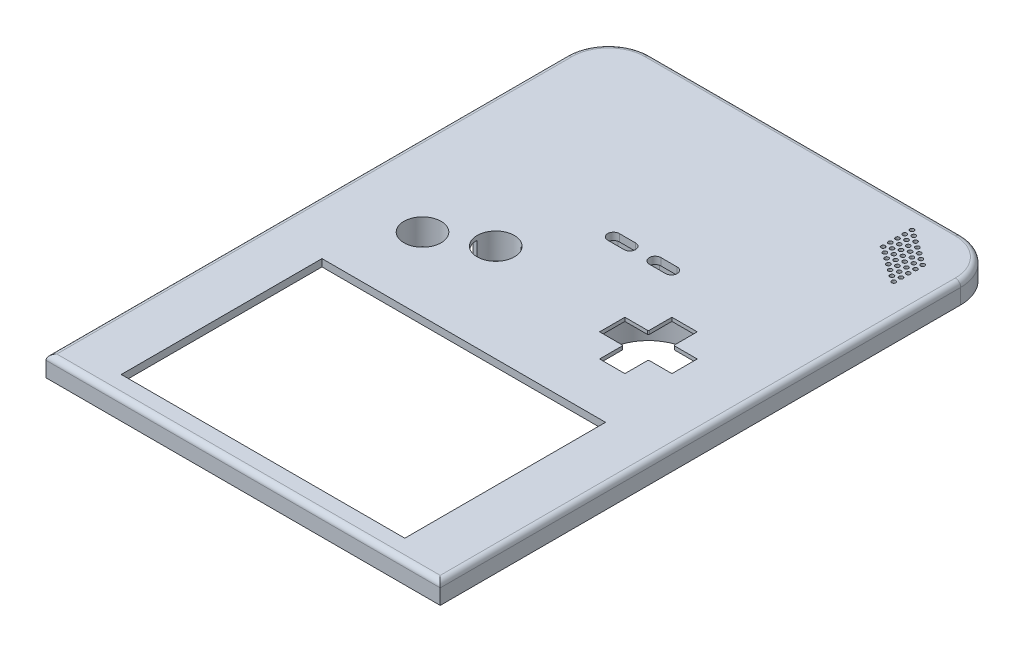
SolidWorks part; units mm, degrees
ref_plane "Front Plane" through (0, 0, 0) normal (0, 0, 1) x (1, 0, 0)
ref_plane "Top Plane" through (0, 0, 0) normal (0, 1, 0) x (1, 0, 0)
ref_plane "Right Plane" through (0, 0, 0) normal (1, 0, 0) x (0, 0, -1)
sketch "Sketch1" plane through (0, 0, 0) normal (0, 1, 0) x (1, 0, 0)
  line L1 (-54.5, 77.75) -> (54.5, 77.75)
  line L2 (-54.5, 77.75) -> (-54.5, -77.75)
  line L3 (-54.5, -77.75) -> (54.5, -77.75)
  line L4 (54.5, 77.75) -> (54.5, -77.75)
  line L5 (-54.5, 77.75) -> (54.5, -77.75) construction
  line L6 (-54.5, -77.75) -> (54.5, 77.75) construction
  point P0 (0, 0)
  dimension "D1" = 109
  dimension "D2" = 155.5
extrude "Boss-Extrude1" add sketch "Sketch1" along normal blind 5.7
sketch "Sketch2" plane through (0, 0, 0) normal (0, -1, 0) x (-1, 0, 0)
  line L1 (-52.45, 75.7) -> (52.45, 75.7)
  line L2 (-52.45, 75.7) -> (-52.45, -75.7)
  line L3 (-52.45, -75.7) -> (52.45, -75.7)
  line L4 (52.45, 75.7) -> (52.45, -75.7)
  line L5 (-52.45, 75.7) -> (52.45, -75.7) construction
  line L6 (-52.45, -75.7) -> (52.45, 75.7) construction
  point P0 (0, 0)
  dimension "D1" = 151.4
  dimension "D2" = 104.9
extrude "Cut-Extrude1" cut sketch "Sketch2" against normal blind 3.7
sketch "Sketch3" plane through (0, 5.7, 0) normal (0, 1, 0) x (1, 0, 0)
  line L1 (42.9, 66.15) -> (54.5, 66.15)
  line L2 (54.5, -77.75) -> (54.5, 77.75) construction
  line L4 (31.3, 66.15) -> (31.3, 77.75)
  line L7 (54.5, 66.15) -> (54.5, 77.75)
  line L8 (54.5, 77.75) -> (42.9, 77.75)
  line L9 (42.9, 77.75) -> (42.9, 66.15)
  line L10 (54.5, -77.75) -> (54.5, 77.75) construction
  line L11 (54.5, 77.75) -> (-54.5, 77.75) construction
  line L12 (0, -77.75) -> (0, 77.75) construction
  line L17 (-54.5, -77.75) -> (54.5, -77.75) construction
  line L19 (54.5, 77.75) -> (-54.5, 77.75) construction
  line L21 (-54.5, 77.75) -> (-42.9, 77.75)
  line L22 (-54.5, 66.15) -> (-54.5, 77.75)
  line L25 (-42.9, 77.75) -> (-42.9, 66.15)
  line L26 (-42.9, 66.15) -> (-54.5, 66.15)
  circle A1 centre (42.9, 66.15) radius 11.6
  circle A2 centre (42.9, 66.15) radius 9.55
  circle A5 centre (-42.9, 66.15) radius 9.55
  circle A6 centre (-42.9, 66.15) radius 11.6
  line M2 (54.5, -77.75) -> (54.5, 77.75)
  line M3 (54.5, 77.75) -> (-54.5, 77.75)
  line M4 (-54.5, 77.75) -> (-54.5, -77.75)
  dimension "D1" = 23.2
  dimension "D2" = 19.1
  dimension "D3" = 23.2
extrude "Cut-Extrude3" cut sketch "Sketch3" against normal through all contours A1 M2 M3 region at (51.9089, 5.7, -75.1589)
sketch "Sketch15" plane through (0, 3.7, 0) normal (0, -1, 0) x (1, 0, 0)
  line L5 (42.9, -77.75) -> (-54.5, -77.75) construction
  line L8 (54.5, 77.75) -> (54.5, -66.15) construction
  circle A0 centre (41.14, -64.39) radius 12.3
  circle A1 centre (41.14, -64.39) radius 11.3
  dimension "D1" = 24.6
  dimension "D2" = 22.6
  dimension "D3" = 13.36
  dimension "D4" = 13.36
extrude "Boss-Extrude27" add sketch "Sketch15" along normal blind 3.15
sketch "Sketch4" plane through (0, 5.7, 0) normal (0, 1, 0) x (1, 0, 0)
  line L0 (54.5, -44.5) -> (-54.5, -44.5) construction
  line L1 (-54.5, -77.75) -> (54.5, -77.75) construction
  line L4 (-54.5, 77.75) -> (-54.5, -77.75) construction
  line L5 (54.5, -77.75) -> (54.5, 66.15) construction
  line L7 (39.2, -72.25) -> (-39.2, -72.25)
  line L8 (39.2, -72.25) -> (39.2, -16.75)
  line L9 (39.2, -16.75) -> (-39.2, -16.75)
  line L10 (-39.2, -72.25) -> (-39.2, -16.75)
  line L11 (39.2, -72.25) -> (-39.2, -16.75) construction
  line L12 (39.2, -16.75) -> (-39.2, -72.25) construction
  point P8 (0, -44.5)
  dimension "D1" = 78.4
  dimension "D2" = 55.5
  dimension "D3" = 5.5
extrude "Cut-Extrude4" cut sketch "Sketch4" against normal through all
sketch "Sketch5" plane through (0, 3.7, 0) normal (0, -1, 0) x (1, 0, 0)
  line L0 (-52.45, 0) -> (52.45, 0) construction
  line L1 (49.1775, 69.4234) -> (46.5741, 71.5316)
  line L2 (46.5741, 71.5316) -> (43.4466, 70.3311)
  line L3 (43.4466, 70.3311) -> (42.9225, 67.0223)
  line L4 (42.9225, 67.0223) -> (45.5259, 64.9141)
  line L5 (45.5259, 64.9141) -> (48.6534, 66.1146)
  line L6 (48.6534, 66.1146) -> (49.1775, 69.4234)
  line L7 (-52.45, 75.7) -> (-52.45, -75.7) construction
  line L8 (52.45, -72.7346) -> (52.45, -69.2247) construction
  line L12 (-49.1775, -69.4234) -> (-46.5741, -71.5316)
  line L13 (-48.6534, 66.1146) -> (-49.1775, 69.4234)
  line L14 (-45.5259, 64.9141) -> (-48.6534, 66.1146)
  line L15 (-42.9225, 67.0223) -> (-45.5259, 64.9141)
  line L16 (-43.4466, 70.3311) -> (-42.9225, 67.0223)
  line L17 (-46.5741, 71.5316) -> (-43.4466, 70.3311)
  line L18 (-49.1775, 69.4234) -> (-46.5741, 71.5316)
  line L19 (-46.5741, -71.5316) -> (-43.4466, -70.3311)
  line L20 (-43.4466, -70.3311) -> (-42.9225, -67.0223)
  line L21 (-42.9225, -67.0223) -> (-45.5259, -64.9141)
  line L22 (-45.5259, -64.9141) -> (-48.6534, -66.1146)
  line L23 (-48.6534, -66.1146) -> (-49.1775, -69.4234)
  circle A0 centre (46.05, 68.2228) radius 2.4682 construction
  circle A1 centre (46.05, 68.2228) radius 3.85
  circle A2 centre (-46.05, 68.2228) radius 2.4682 construction
  circle A3 centre (-46.05, 68.2228) radius 3.85
  circle A4 centre (-46.05, -68.2228) radius 2.4682 construction
  circle A5 centre (-46.05, -68.2228) radius 3.85
  point P40 (0, 0)
  dimension "D2" = 7.7
  dimension "D1" = 6.7
  dimension "D3" = 92.1
extrude "Boss-Extrude3" add sketch "Sketch5" along normal blind 3.05
sketch "Sketch8" plane through (0, 3.7, 0) normal (0, -1, 0) x (1, 0, 0)
  line L0 (-40.65, 16.75) -> (40.65, 16.75) construction
  line L1 (40.65, 16.75) -> (40.65, -33.25) construction
  line L2 (40.65, -33.25) -> (-40.65, -33.25) construction
  line L3 (-40.65, -33.25) -> (-40.65, 16.75) construction
  line L4 (52.45, 11.7609) -> (-52.45, 11.7609) construction
  line L5 (0.4, -28.75) -> (-4.1, -28.75) construction
  line L6 (52.45, -59.5553) -> (52.45, 75.7) construction
  line L7 (-52.45, 75.7) -> (-52.45, -75.7) construction
  line L8 (-39.2, 16.75) -> (39.2, 16.75) construction
  line L9 (0.4, -29.75) -> (-4.1, -29.75)
  line L10 (0.4, -27.75) -> (-4.1, -27.75)
  line L11 (11.9, -28.75) -> (7.4, -28.75) construction
  line L12 (11.9, -29.75) -> (7.4, -29.75)
  line L13 (11.9, -27.75) -> (7.4, -27.75)
  circle A0 centre (26.715, -7.585) radius 11.75
  circle A1 centre (26.715, -7.585) radius 12.85
  circle A2 centre (-31.65, -3.5) radius 6.25
  circle A3 centre (-31.65, -3.5) radius 5.15
  circle A4 centre (-18.15, -10.25) radius 6.25
  circle A5 centre (-18.15, -10.25) radius 5.15
  arc A6 (0.4, -29.75) -> (0.4, -27.75) centre (0.4, -28.75) ccw
  arc A7 (-4.1, -27.75) -> (-4.1, -29.75) centre (-4.1, -28.75) ccw
  arc A8 (11.9, -29.75) -> (11.9, -27.75) centre (11.9, -28.75) ccw
  arc A9 (7.4, -27.75) -> (7.4, -29.75) centre (7.4, -28.75) ccw
  point P11 (0, 16.75)
  point P14 (0, 11.7609)
  point P25 (-1.85, -28.75)
  point P33 (9.65, -28.75)
  dimension "D1" = 23.5
  dimension "D2" = 25.7
  dimension "D10" = 12.5
  dimension "D11" = 10.3
  dimension "D14" = 12.5
  dimension "D15" = 10.3
  dimension "D19" = 1
  dimension "D20" = 1
  dimension "D18" = 7
  dimension "D3" = 50
  dimension "D4" = 81.3
  dimension "D5" = 0
  dimension "D6" = 24.335
  dimension "D7" = 67.365
  dimension "D8" = 72.3
  dimension "D9" = 20.25
  dimension "D12" = 58.8
  dimension "D13" = 27
  dimension "D16" = 45.5
  dimension "D21" = 4.5
  dimension "D22" = 4.5
extrude "Boss-Extrude5" add sketch "Sketch8" along normal blind 5.15
sketch "Sketch9" plane through (0, 3.7, 0) normal (0, -1, 0) x (1, 0, 0)
  line L0 (16.1084, 3.0216) -> (37.3216, -18.1916) construction
  line L1 (26.715, 4.165) -> (26.715, -7.585) construction
  circle A0 centre (26.715, -7.585) radius 11.75 construction
  circle A1 centre (16.1084, 3.0216) radius 1
  circle A2 centre (37.3216, -18.1916) radius 1
  point P7 (26.715, -7.585)
  dimension "D2" = 2
  dimension "D1" = 30
extrude "Boss-Extrude6" add sketch "Sketch9" along normal blind 5.6
sketch "Sketch11" plane through (0, 3.7, 0) normal (0, -1, 0) x (1, 0, 0)
  line L0 (14.965, -7.585) -> (38.465, -7.585) construction
  line L2 (26.715, 2.415) -> (26.715, -17.585) construction
  line L4 (30.215, -4.085) -> (30.215, 2.415)
  line L5 (30.215, 2.415) -> (23.215, 2.415)
  line L6 (23.215, -4.085) -> (23.215, 2.415)
  line L7 (30.215, -4.085) -> (36.715, -4.085)
  line L9 (30.215, -11.085) -> (36.715, -11.085)
  line L10 (36.715, -4.085) -> (36.715, -11.085)
  line L12 (23.215, -11.085) -> (23.215, -17.585)
  line L13 (23.215, -17.585) -> (30.215, -17.585)
  line L14 (30.215, -11.085) -> (30.215, -17.585)
  line L15 (23.215, -4.085) -> (16.715, -4.085)
  line L17 (23.215, -11.085) -> (16.715, -11.085)
  line L18 (16.715, -4.085) -> (16.715, -11.085)
  line L19 (16.715, -7.585) -> (14.965, -7.585) construction
  line L20 (16.715, -7.585) -> (36.715, -7.585) construction
  circle A0 centre (26.715, -7.585) radius 11.75 construction
  point P4 (26.715, -7.585)
  point P9 (26.715, -7.585)
  point P25 (26.715, -7.585)
  dimension "D1" = 7
  dimension "D2" = 6.5
extrude "Cut-Extrude7" cut sketch "Sketch11" against normal up to next
sketch "Sketch12" plane through (0, 3.7, 0) normal (0, -1, 0) x (1, 0, 0)
  circle A0 centre (26.715, -7.585) radius 11.75
extrude "Cut-Extrude8" cut sketch "Sketch12" against normal blind 1
sketch "Sketch13" plane through (0, 3.7, 0) normal (0, -1, 0) x (-1, 0, 0)
  line L0 (31.65, 3.5) -> (18.15, 10.25) construction
  line L2 (12.2427, -18.4396) -> (20.5806, -1.7638) construction
  circle A0 centre (31.65, 3.5) radius 5.15
  circle A1 centre (18.15, 10.25) radius 5.15
  dimension "D1" = 10.3
extrude "Cut-Extrude9" cut sketch "Sketch13" against normal up to next
extrude "Boss-Extrude10" add sketch "Sketch3<9>" against normal up to surface (5.7 mm away) contours A2 L1 A1 L9 region at (49.6533, 5.7, -72.9033) up to face at (9.3041, 0, -13.9541)
sketch "Sketch3<9>" plane through (0, 5.7, 0) normal (0, 1, 0) x (1, 0, 0) same geometry as "Sketch3"
sketch "Sketch16" plane through (0, 3.7, 0) normal (0, -1, 0) x (-1, 0, 0)
  circle A0 centre (-35.5274, 63.6495) radius 0.562
  circle A1 centre (-37.1657, 62.5023) radius 0.562
  circle A2 centre (-38.804, 61.3552) radius 0.562
  circle A3 centre (-40.4423, 60.208) radius 0.562
  circle A4 centre (-42.0806, 59.0609) radius 0.562
  circle A5 centre (-43.7189, 57.9137) radius 0.562
  circle A6 centre (-45.3572, 56.7666) radius 0.562
  circle A8 centre (-37.1657, 64.5023) radius 0.562
  circle A9 centre (-38.804, 63.3552) radius 0.562
  circle A10 centre (-40.4423, 62.208) radius 0.562
  circle A11 centre (-42.0806, 61.0609) radius 0.562
  circle A12 centre (-43.7189, 59.9137) radius 0.562
  circle A13 centre (-45.3572, 58.7666) radius 0.562
  circle A15 centre (-37.1657, 66.5023) radius 0.562
  circle A16 centre (-38.804, 65.3552) radius 0.562
  circle A17 centre (-40.4423, 64.208) radius 0.562
  circle A18 centre (-42.0806, 63.0609) radius 0.562
  circle A19 centre (-43.7189, 61.9137) radius 0.562
  circle A20 centre (-45.3572, 60.7666) radius 0.562
  circle A22 centre (-37.1657, 68.5023) radius 0.562
  circle A23 centre (-38.804, 67.3552) radius 0.562
  circle A24 centre (-40.4423, 66.208) radius 0.562
  circle A25 centre (-42.0806, 65.0609) radius 0.562
  circle A26 centre (-43.7189, 63.9137) radius 0.562
  circle A27 centre (-45.3572, 62.7666) radius 0.562
  circle A29 centre (-37.1657, 70.5023) radius 0.562
  circle A30 centre (-38.804, 69.3552) radius 0.562
  circle A31 centre (-40.4423, 68.208) radius 0.562
  circle A32 centre (-42.0806, 67.0609) radius 0.562
  circle A33 centre (-43.7189, 65.9137) radius 0.562
  circle A34 centre (-45.3572, 64.7666) radius 0.562
  circle A36 centre (-35.5274, 65.6495) radius 0.562
  circle A37 centre (-35.5274, 67.6495) radius 0.562
  circle A38 centre (-35.5274, 69.6495) radius 0.562
  circle A39 centre (-35.5274, 71.6495) radius 0.562
  dimension "D1" = 7
  dimension "D2" = 5
extrude "Cut-Extrude13" cut sketch "Sketch16" against normal up to surface (2 mm away) up to face at (9.0605, 5.7, -13.7105)
fillet "Fillet3" radius 0.25 4 edges at (30.215, 5.2, -11.085) (23.215, 5.2, -11.085) (23.215, 5.2, -4.085) (30.215, 5.2, -4.085)
sketch "Sketch17" plane through (0, -1.45, 0) normal (0, -1, 0) x (-1, 0, 0)
  line L0 (26.5, 3.5) -> (36.8, 3.5) construction
  line L1 (31.65, -1.65) -> (31.65, 8.65) construction
  line L6 (35.2, 2.35) -> (38.4, 2.35)
  line L7 (35.2, 2.35) -> (35.2, 4.65)
  line L12 (35.2, 4.65) -> (38.4, 4.65)
  line L13 (38.4, 2.35) -> (38.4, 4.65)
  line L14 (35.2, 2.35) -> (38.4, 4.65) construction
  line L15 (35.2, 4.65) -> (38.4, 2.35) construction
  line L16 (28.1, 4.65) -> (24.9, 4.65)
  line L17 (24.9, 2.35) -> (24.9, 4.65)
  line L18 (28.1, 2.35) -> (24.9, 2.35)
  line L19 (28.1, 2.35) -> (28.1, 4.65)
  line L20 (31.65, 3.5) -> (25.6278, 6.7585)
  line L21 (31.65, 3.5) -> (31.65, 10.3473)
  circle A0 centre (31.65, 3.5) radius 6.25 construction
  arc A1 (27.1205, 5.9508) -> (31.65, 8.65) centre (31.65, 3.5) ccw
  arc A2 (37.8782, 2.35) -> (37.9311, 2.687) centre (31.65, 3.5) ccw
  circle A3 centre (31.65, 3.5) radius 5.15 construction
  circle A4 centre (31.65, 3.5) radius 6.8473
  dimension "D1" = 13.5
  dimension "D2" = 2.3
sketch "Sketch18" plane through (0, -1.45, 0) normal (0, -1, 0) x (1, 0, 0)
  line L0 (-17.15, -4.1) -> (-12, -4.1) construction
  line L1 (-12, -4.1) -> (-12, -14.4) construction
  line L2 (-18.15, -10.25) -> (-11.6453, -3.7453) construction
  line L3 (-12, -4.1) -> (-6.3147, -4.1) construction
  line L4 (-18.15, -5.1) -> (-18.15, -15.4) construction
  line L5 (1.8227, -7.9997) -> (-7.0385, 0.8615) construction
  line L6 (-16.1372, -6.0512) -> (-14.5109, -7.6775)
  line L7 (-16.1372, -6.0512) -> (-12.4584, -2.9321)
  line L8 (-12.4584, -2.9321) -> (-10.8321, -4.5584)
  line L9 (-14.5109, -7.6775) -> (-10.8321, -4.5584)
  line L10 (-16.1372, -6.0512) -> (-10.8321, -4.5584) construction
  line L11 (-12.4584, -2.9321) -> (-14.5109, -7.6775) construction
  line L12 (-18.15, -10.25) -> (-21.5365, -3.165) construction
  line L13 (-23.3, -10.25) -> (-13, -10.25) construction
  line L22 (-18.15, -10.25) -> (-21.5365, -3.165)
  line L23 (-18.15, -10.25) -> (-26.0027, -10.25)
  line L24 (-12.4584, -17.5679) -> (-10.8321, -15.9416)
  line L25 (-14.5109, -12.8225) -> (-10.8321, -15.9416)
  line L26 (-16.1372, -14.4488) -> (-14.5109, -12.8225)
  line L27 (-16.1372, -14.4488) -> (-12.4584, -17.5679)
  arc A5 (-21.5365, -3.165) -> (-26.0027, -10.25) centre (-18.15, -10.25) ccw
  arc A6 (-13.1539, -13.973) -> (-12, -9.25) centre (-18.15, -10.25) ccw
  arc A7 (-12.2448, -3.1458) -> (-12.4839, -2.9537) centre (-18.15, -10.25) ccw
  circle A8 centre (-18.15, -10.25) radius 7.8527
  circle A9 centre (-18.15, -10.25) radius 5.15 construction
  arc A10 (-24.3808, -10.25) -> (-14.8534, -15.5373) centre (-18.15, -10.25) ccw
  arc A12 (-14.8534, -4.9627) -> (-20.837, -4.6284) centre (-18.15, -10.25) ccw
  point P26 (-18.15, -10.25)
  dimension "D3" = 15.7055
  dimension "D1" = 45
  dimension "D2" = 2.3
extrude "Cut-Extrude24" cut sketch "Sketch18" against normal blind 6 contours L23 A5 L22 | L7 L6 L9 L8 | L24 L25 L26 L27
sketch "Sketch19" plane through (0, 3.7, 0) normal (0, -1, 0) x (1, 0, 0)
  line L0 (-31.65, -3.5) -> (-31.65, -20.3718) construction
  line L1 (-30.5647, -9.655) -> (-27.7678, -25.5172) construction
  line L2 (-30.5647, -9.655) -> (-30.2608, -11.3785)
  circle A0 centre (-31.65, -3.5) radius 6.25
  circle A1 centre (-30.2608, -11.3785) radius 1
  dimension "D3" = 2
  dimension "D1" = 10
  dimension "D2" = 1.75
extrude "Boss-Extrude28" add sketch "Sketch19" along normal blind 5.6 contours A1 region at (-29.6362, 3.7, -10.6341)
chamfer "Chamfer1" distance 0.25 angle 45 3 edges at (37.3216, -1.9, -19.1916) (16.1084, -1.9, 2.0216) (-30.2608, -1.9, -12.3785)
extrude "Cut-Extrude18" cut sketch "Sketch3<12>" against normal through all contours A6 M4 M3 region at (-51.9089, 5.7, -75.1589)
sketch "Sketch3<12>" plane through (0, 5.7, 0) normal (0, 1, 0) x (1, 0, 0) same geometry as "Sketch3"
extrude "Boss-Extrude29" add sketch "Sketch3<14>" against normal up to surface (5.7 mm away) contours A6 L26 A5 L25 region at (-49.6533, 5.7, -72.9033) up to face at (-0.2384, 0, -23.0185)
sketch "Sketch3<14>" plane through (0, 5.7, 0) normal (0, 1, 0) x (1, 0, 0) same geometry as "Sketch3"
fillet "Fillet2" radius 1.5 6 edges at (0, 5.7, -77.75) (51.1024, 5.7, -74.3524) (54.5, 5.7, 5.8) (0, 5.7, 77.75) (-54.5, 5.7, 5.8) (-51.1024, 5.7, -74.3524)
sketch "Sketch22" plane through (0, 3.7, 0) normal (0, -1, 0) x (1, 0, 0)
  line L0 (6.4, -29) -> (12.9, -29) construction
  line L1 (6.4, -27) -> (12.9, -27)
  line L2 (6.4, -31) -> (12.9, -31)
  line L3 (-5.1, -29) -> (1.4, -29) construction
  line L4 (-5.1, -27) -> (1.4, -27)
  line L5 (-5.1, -31) -> (1.4, -31)
  line L6 (12.8148, -29) -> (-5.1852, -29) construction
  line L7 (12.8148, -32) -> (-5.1852, -32)
  line L8 (12.8148, -26) -> (-5.1852, -26)
  arc A2 (6.4, -27) -> (6.4, -31) centre (6.4, -29) ccw
  arc A3 (12.9, -31) -> (12.9, -27) centre (12.9, -29) ccw
  arc A6 (-5.1, -27) -> (-5.1, -31) centre (-5.1, -29) ccw
  arc A7 (1.4, -31) -> (1.4, -27) centre (1.4, -29) ccw
  arc A8 (12.8148, -32) -> (12.8148, -26) centre (12.8148, -29) ccw
  arc A9 (-5.1852, -26) -> (-5.1852, -32) centre (-5.1852, -29) ccw
  point P2 (-5.9688, -29)
  point P3 (0, 0)
  point P4 (13.6531, -29)
  point P5 (13.5984, -29)
  point P8 (9.65, -29)
  point P21 (-1.85, -29)
  point P28 (3.8148, -29)
  dimension "D1" = 2
  dimension "D2" = 2
  dimension "D3" = 3
  dimension "D4" = 18
extrude "Boss-Extrude30" add sketch "Sketch22" along normal blind 3.15 contours L8 A8 L7 A9 | L2 A3 L1 A2 | L5 A7 L4 A6
sketch "Sketch23" plane through (0, -1.45, 0) normal (0, -1, 0) x (1, 0, 0)
  line L0 (-4.1, -28.75) -> (0.4, -28.75) construction
  line L1 (-4.1, -27.15) -> (0.4, -27.15)
  line L2 (-4.1, -30.35) -> (0.4, -30.35)
  line L3 (7.4, -28.75) -> (11.9, -28.75) construction
  line L4 (7.4, -27.15) -> (11.9, -27.15)
  line L5 (7.4, -30.35) -> (11.9, -30.35)
  arc A0 (-4.1, -27.15) -> (-4.1, -30.35) centre (-4.1, -28.75) ccw
  arc A1 (0.4, -30.35) -> (0.4, -27.15) centre (0.4, -28.75) ccw
  arc A2 (7.4, -27.15) -> (7.4, -30.35) centre (7.4, -28.75) ccw
  arc A3 (11.9, -30.35) -> (11.9, -27.15) centre (11.9, -28.75) ccw
  point P4 (-1.85, -28.75)
  point P13 (9.65, -28.75)
  dimension "D1" = 1.6
  dimension "D2" = 1.6
extrude "Cut-Extrude26" cut sketch "Sketch23" against normal through all
